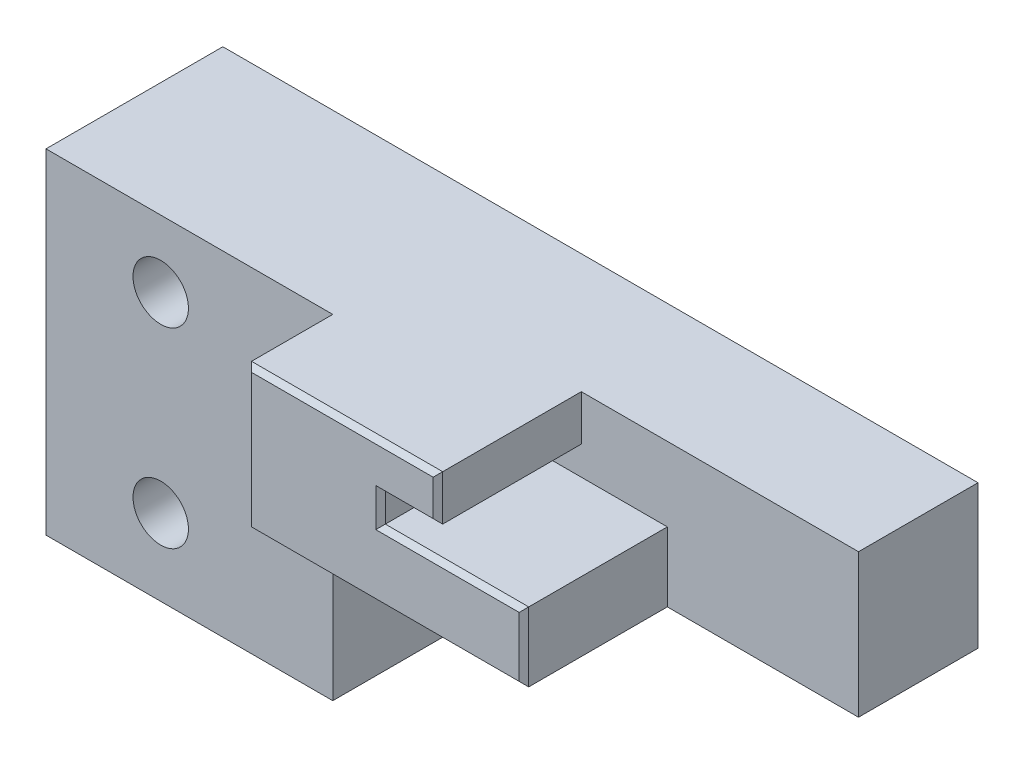
SolidWorks part; units mm, degrees
ref_plane "Front Plane" through (0, 0, 0) normal (0, 0, 1) x (1, 0, 0)
ref_plane "Top Plane" through (0, 0, 0) normal (0, 1, 0) x (1, 0, 0)
ref_plane "Right Plane" through (0, 0, 0) normal (1, 0, 0) x (0, 0, -1)
sketch "Sketch1" plane through (0, 0, 0) normal (0, 0, 1) x (1, 0, 0)
  line L4 (0, 0) -> (6, 0)
  line L9 (6, 0) -> (6, -4.75)
  line L10 (6, -4.75) -> (0, -4.75)
  line L11 (0, -4.75) -> (0, -15)
  line L12 (0, -15) -> (-44, -15)
  line L13 (-44, -15) -> (-44, 0)
  line L14 (-44, 0) -> (0, 0)
  line L15 (0, -7.75) -> (15, -7.75)
  line L16 (15, -7.75) -> (15, -15)
  line L17 (15, -15) -> (0, -15)
  dimension "D2" = 6
  dimension "D1" = 4.75
  dimension "D3" = 15
  dimension "D4" = 50
  dimension "D5" = 3
  dimension "D6" = 15
extrude "Boss-Extrude1" add sketch "Sketch1" along normal blind 15 contours L14 L13 L12 L11 L10 L9 L4 | L17 L16 L15 L11 region at (-20.9651, -7.2879, 0) region at (7.5, -11.375, 0)
sketch "Sketch4" plane through (0, 0, 0) normal (0, 0, -1) x (-1, 0, 0)
  line L1 (44, 0) -> (-15, 0)
  line L2 (44, 0) -> (44, -15)
  line L3 (44, -15) -> (-15, -15)
  line L4 (-15, 0) -> (-15, -15) construction
  line L5 (14.5, -15) -> (14.5, 0) construction
  line L6 (44, -7.5) -> (-15, -7.5) construction
  line L7 (44, -15) -> (44, 0) construction
  line L8 (44, 0) -> (-6, 0) construction
  line L9 (-15, 0) -> (-35, 0)
  line L10 (-15, 0) -> (-15, -15) construction
  line L11 (-15, -15) -> (-35, -15)
  line L12 (-35, 0) -> (-35, -15)
  line L13 (-25, -15) -> (-25, 0) construction
  line L14 (-15, -7.5) -> (-35, -7.5) construction
  point P166 (-25, -7.5)
  point P252 (14.5, -7.5)
  dimension "D1" = 20
extrude "Boss-Extrude4" add sketch "Sketch4" along normal blind 13
sketch "Sketch5" plane through (0, 0, 15) normal (0, 0, 1) x (1, 0, 0)
  line L0 (6, 0) -> (35, 0) construction
  line L1 (0, -7.75) -> (15, -7.75)
  line L2 (0, -7.75) -> (0, 0)
  line L3 (0, 0) -> (15, 0)
  line L4 (15, -7.75) -> (15, 0)
  line L5 (7.5, 0) -> (7.5, -7.75) construction
  line L6 (0, -3.875) -> (15, -3.875) construction
  point P4 (15, 0)
  point P144 (7.5, -3.875)
extrude "Boss-Extrude5" [suppressed] add sketch "Sketch5" against normal blind 2.25
sketch "Sketch6" plane through (0, 0, 15) normal (0, 0, 1) x (1, 0, 0)
  line L0 (15, -15) -> (-44, -15) construction
  line L1 (-44, 0) -> (-14, 0)
  line L2 (-44, 0) -> (-44, -15)
  line L3 (-44, -15) -> (-14, -15)
  line L4 (-14, 0) -> (-14, -15)
  line L5 (-29, -15) -> (-29, 0) construction
  line L6 (-44, -7.5) -> (-14, -7.5) construction
  point P168 (-29, -7.5)
  dimension "D1" = 30
extrude "Cut-Extrude1" cut sketch "Sketch6" against normal offset from surface (9 mm away) 19 up to face at (-4.5, -7.5, -13)
sketch "Sketch7" plane through (0, 0, 6) normal (0, 0, 1) x (1, 0, 0)
  line L0 (-44, 0) -> (-14, 0) construction
  line L1 (-14, -15) -> (-44, -15)
  line L2 (-14, -15) -> (-14, -35)
  line L3 (-14, -35) -> (-44, -35)
  line L4 (-44, -15) -> (-44, -35)
  line L5 (-29, -35) -> (-29, -15) construction
  line L6 (-14, -25) -> (-44, -25) construction
  point P196 (-29, -25)
  dimension "D1" = 35
extrude "Boss-Extrude6" add sketch "Sketch7" against normal up to surface (19 mm away) up to face at (-4.5, -7.5, -13)
hole_wizard "M5 Clearance Hole1" positions "Sketch8" profile "Sketch9" hole size "M5" standard "ANSI Metric" end condition through all
sketch "Sketch8" plane through (0, 0, 6) normal (0, 0, 1) x (1, 0, 0)
  line L0 (-44, 0) -> (-14, 0) construction
  point P0 (-32, -7)
  point P2 (-32, -27)
  dimension "D1" = 20
  dimension "D2" = 32
  dimension "D3" = 7
sketch "Sketch9" plane through (-32, -7, 6) normal (1, 0, 0) x (0, -1, 0)
  line L0 (0, 0) -> (0, 19)
  line L1 (0, 19) -> (2.9, 19)
  line L2 (2.9, 19) -> (2.9, 0)
  line L5 (2.9, 0) -> (0, 0)
  line L11 (0, -6.35) -> (0, 107.95) construction
  dimension "Thru Hole Dia." = 5.8
  dimension "Thru Hole Depth" = 19
chamfer "Chamfer1" distance 0.5 angle 45 16 edges at (-29, -35, -13) (-14, -25, -13) (10.5, -15, -13) (35, -7.5, -13) (-4.5, 0, -13) (-44, -17.5, -13) (-29.1, -27, -13) (-29.1, -7, -13) (-4, 0, 15) (6, -2.375, 15) (3, -4.75, 15) (0, -6.25, 15) (7.5, -7.75, 15) (15, -11.375, 15) (0.5, -15, 15) (-14, -7.5, 15)
